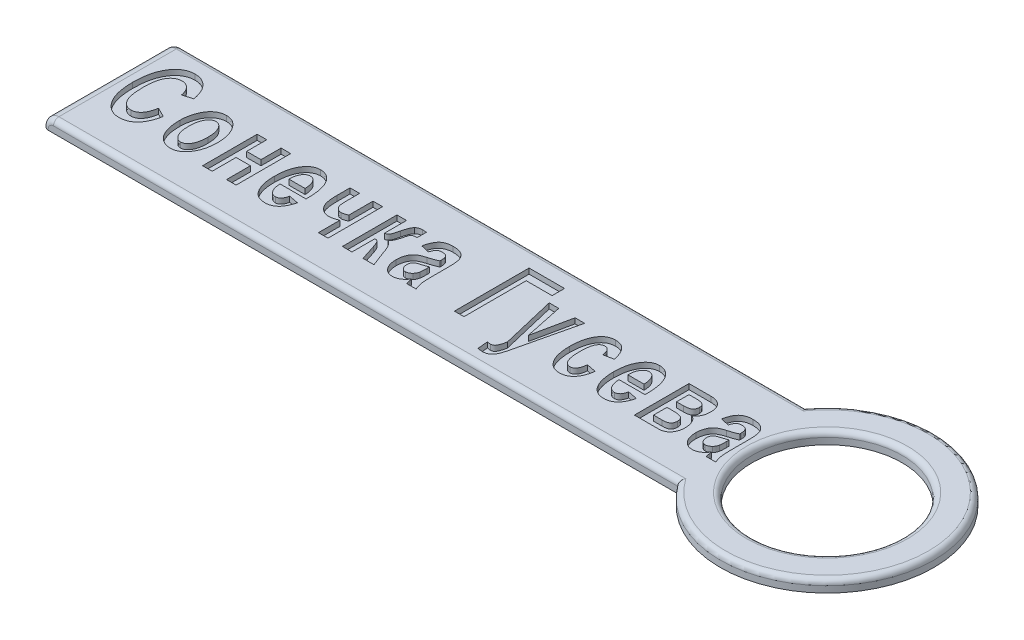
SolidWorks part; units mm, degrees
ref_plane "Спереди" through (0, 0, 0) normal (0, 0, 1) x (1, 0, 0)
ref_plane "Сверху" through (0, 0, 0) normal (0, 1, 0) x (1, 0, 0)
ref_plane "Справа" through (0, 0, 0) normal (1, 0, 0) x (0, 0, -1)
other "Configuration Table"
sketch "Эскиз1" plane through (0, 0, 0) normal (0, 1, 0) x (1, 0, 0)
  line L1 (0, 0) -> (120, 0)
  line L2 (0, 0) -> (0, 24)
  line L3 (0, 24) -> (120, 24)
  line L4 (120, 0) -> (120, 24)
  line L5 (60, 24) -> (60, 0) construction
  line L6 (0, 12) -> (120, 12) construction
  circle A0 centre (135, 12) radius 20
  point P436 (60, 12)
  dimension "D4" = 40
  dimension "D1" = 24
  dimension "D2" = 120
  dimension "D3" = 15
extrude "Бобышка-Вытянуть1" add sketch "Эскиз1" along normal blind 2.2 contours A0 L3 L2 L1 | L3 A0 L1 L4 | L1 A0 L3 L4 region at (58.1434, 0, -12) region at (117.9531, 0, -12) region at (136.3056, 0, -12)
sketch "Эскиз2" plane through (0, 2.2, 0) normal (0, 1, 0) x (1, 0, 0)
  line L0 (135, -8) -> (135, 32) construction
  line L1 (155, 12) -> (0, 12) construction
  line L2 (0, 0) -> (0, 24) construction
  arc A0 (119, 0) -> (119, 24) centre (135, 12) ccw construction
  circle A1 centre (135, 12) radius 14.065
extrude "Вырез-Вытянуть1" cut sketch "Эскиз2" against normal blind 2.2
sketch "Эскиз3" plane through (0, 2.2, 0) normal (0, 1, 0) x (1, 0, 0)
  text T0 " Сонечка Гусева" font "Arial" height 14
extrude "Вырез-Вытянуть2" cut sketch "Эскиз3" against normal blind 1
fillet "Скругление1" radius 2 1 edges at (0, 2.2, -12)
fillet "Скругление2" radius 2 1 edges at (0, 0, -12)
fillet "Скругление3" radius 1 2 edges at (0.5858, 1.6142, -24) (60.5, 2.2, -24)
fillet "Скругление4" radius 1 2 edges at (0.5858, 1.6142, 0) (60.5, 2.2, 0)
fillet "Скругление5" radius 1 1 edges at (135, 2.2, 2.065)
fillet "Скругление6" radius 1 1 edges at (155, 2.2, -12)
